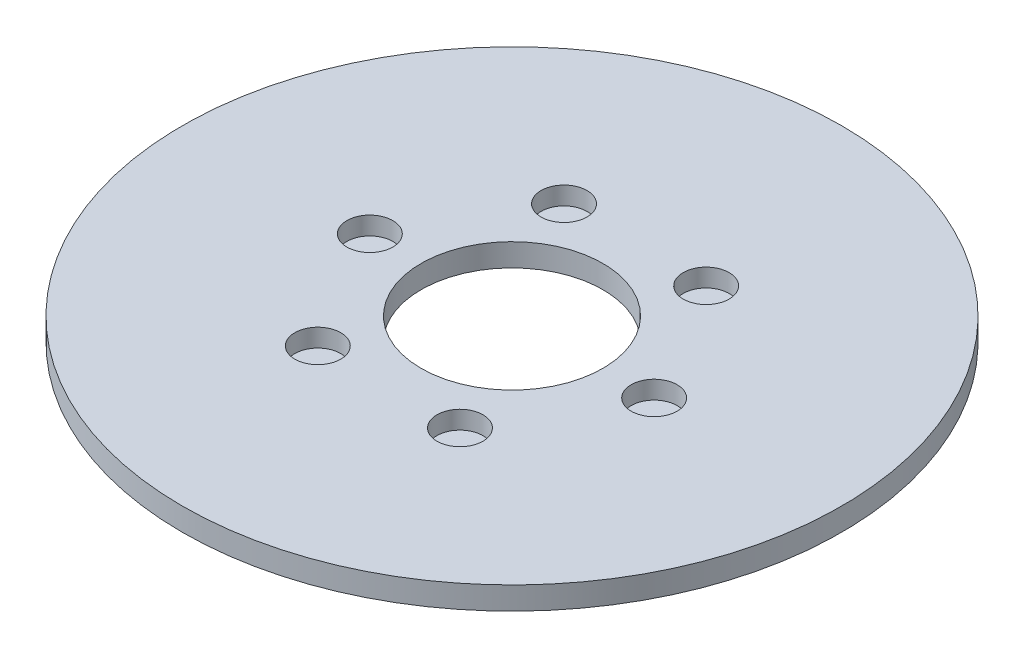
SolidWorks part; units mm, degrees
ref_plane "Front Plane" through (0, 0, 0) normal (0, 0, 1) x (1, 0, 0)
ref_plane "Top Plane" through (0, 0, 0) normal (0, 1, 0) x (1, 0, 0)
ref_plane "Right Plane" through (0, 0, 0) normal (1, 0, 0) x (0, 0, -1)
sketch "Sketch1" plane through (0, 0, 0) normal (0, 1, 0) x (1, 0, 0)
  circle A0 centre (0, 0) radius 72.5
  dimension "FLANGE_OD" = 145
extrude "Boss-Extrude1" add sketch "Sketch1" along normal blind 5
sketch "Sketch2" plane through (0, 0, 0) normal (0, 1, 0) x (1, 0, 0)
  circle A0 centre (0, 0) radius 20
  dimension "BORE_D" = 40
extrude "Cut-Extrude1" cut sketch "Sketch2" along normal through all
sketch "Sketch3" plane through (0, 5, 0) normal (0, 1, 0) x (1, 0, 0)
  circle A0 centre (0, 0) radius 31.2719 construction
  circle A1 centre (-31.2719, 0) radius 5.0524
  dimension "BOLT_D" = 10.1047
  dimension "BOLT_PCD" = 62.5437
extrude "Cut-Extrude2" cut sketch "Sketch3" against normal blind 3.98
pattern_circular "CirPattern1" count 6 over 360 about axis through (0, 0, 0) along (0, 1, 0) of "Cut-Extrude2"
